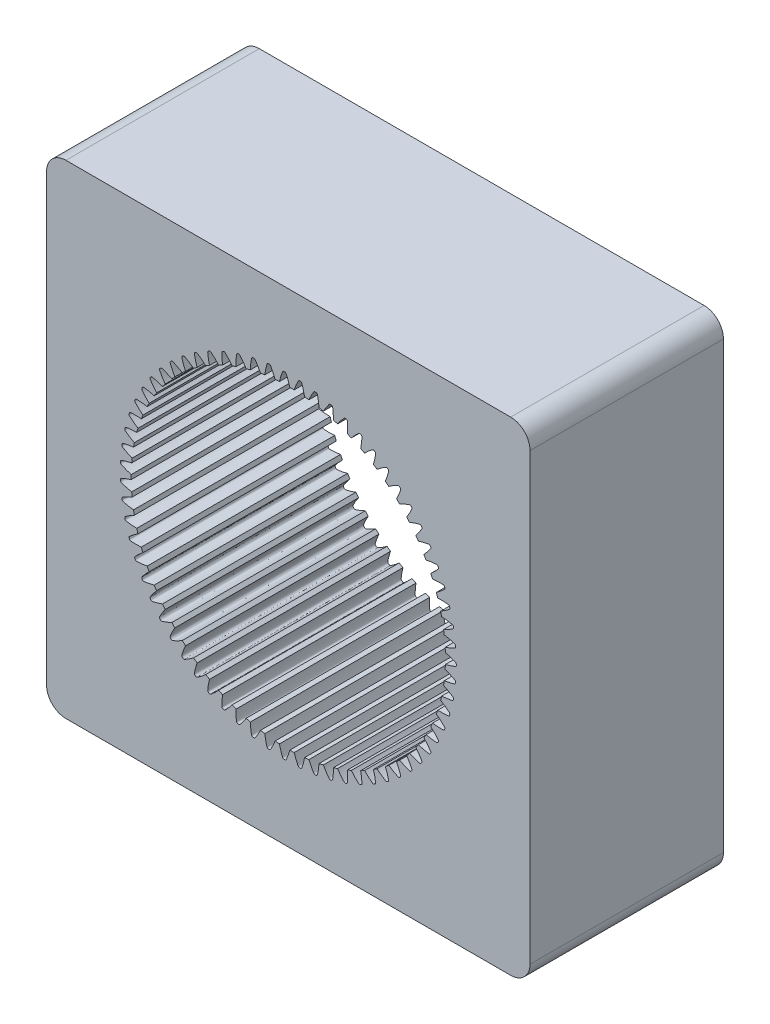
SolidWorks part; units mm, degrees
ref_plane "Front" through (0, 0, 0) normal (0, 0, 1) x (1, 0, 0)
ref_plane "Top" through (0, 0, 0) normal (0, 1, 0) x (1, 0, 0)
ref_plane "Right" through (0, 0, 0) normal (1, 0, 0) x (0, 0, -1)
ref_axis "Ось1" through (0, 0, 50) along (0, 0, -1)
sketch "SketchRevolveRing_Gear_Fixed01" plane through (0, 0, 0) normal (1, 0, 0) x (0, 0, -1)
  line L0 (0, 0) -> (1, 0) construction
  line L1 (-17.5, 16.25) -> (-17.5, 70)
  line L2 (-17.5, 70) -> (2.5, 70)
  line L3 (2.5, 70) -> (2.5, 16.25)
  line L4 (2.5, 16.25) -> (-17.5, 16.25)
  dimension "Side1" = 17.5
  dimension "OutsideRadius" = 70
  dimension "Side2" = 2.5
  dimension "MinorDiameter" = 16.25
revolve "Ring_Gear_Fixed01" add sketch "SketchRevolveRing_Gear_Fixed01" angle 360 about L0
sketch "SketchToothRing_Gear_Fixed01" plane through (0, 0, 0) normal (0, 0, 1) x (1, 0, 0)
  arc A0 (16.1448, -0.5551) -> (16.1448, 0.5551) centre (0, 0) ccw
  spline S0 degree 3 poles (16.1448, 0.5551) (16.203, 0.5437) (16.2937, 0.5237) (16.4187, 0.492) (16.5233, 0.4629) (16.6347, 0.4292) (16.7528, 0.3907) (16.8772, 0.3467) (17.0085, 0.2982) (17.1505, 0.2369) (17.2629, 0.2018) (17.323, 0.1588) (17.3383, 0.1435) (17.3514, 0.1262) (17.3618, 0.1072) (17.3719, 0.0804) (17.3754, 0.0515) (17.3749, 0.0224) (17.3751, 0) (17.3749, -0.0224) (17.3754, -0.0515) (17.3719, -0.0804) (17.3618, -0.1072) (17.3514, -0.1262) (17.3383, -0.1435) (17.323, -0.1588) (17.2629, -0.2018) (17.1505, -0.2369) (17.0085, -0.2982) (16.8772, -0.3467) (16.7528, -0.3907) (16.6347, -0.4292) (16.5233, -0.4629) (16.4187, -0.492) (16.2937, -0.5237) (16.203, -0.5437) (16.1448, -0.5551) knots 0 0 0 0 0.062627 0.098077 0.136285 0.17725 0.220974 0.267455 0.316694 0.36869 0.431293 0.438895 0.446497 0.454098 0.4617 0.469302 0.484196 0.492098 0.5 0.507902 0.515804 0.530698 0.5383 0.545902 0.553503 0.561105 0.568707 0.63131 0.683306 0.732545 0.779026 0.82275 0.863715 0.901923 0.937373 1 1 1 1
extrude "ToothExtrudeCutRing_Gear_Fixed01" cut sketch "SketchToothRing_Gear_Fixed01" against normal blind 2.5 and the other way blind 17.5
ref_axis "Ось2" through (80.9, 0, 0) along (-1, 0, 0)
ref_plane "Плоскость1" through (0, 0, 0) normal (0, 0, -1) x (1, 0, 0)
pattern_circular "PatternRing_Gear_Fixed01" count 67 every 5.373 about axis through (0, 0, 50) along (0, 0, -1) of "ToothExtrudeCutRing_Gear_Fixed01"
sketch "AuxiliarySketchRing_Gear_Fixed01" plane through (0, 0, 0) normal (0, 0, 1) x (1, 0, 0)
  circle A0 centre (0, 0) radius 16.75 construction
  circle A1 centre (0, 0) radius 15.7399 construction
  circle A2 centre (0, 0) radius 17.375 construction
  circle A3 centre (0, 0) radius 16.25 construction
  dimension "PitchDiameter" = 33.5
  dimension "BaseDiameter" = 31.4797
  dimension "MajorDiameter" = 34.75
  dimension "MinorDiameter" = 32.5
sketch "Эскиз4" plane through (0, 0, 17.5) normal (0, 0, 1) x (1, 0, 0)
  line L1 (-25, -25) -> (25, -25)
  line L2 (-25, -25) -> (-25, 25)
  line L3 (-25, 25) -> (25, 25)
  line L4 (25, -25) -> (25, 25)
  line L5 (-25, -25) -> (25, 25) construction
  line L6 (-25, 25) -> (25, -25) construction
  point P0 (0, 0)
  dimension "D1" = 50
  dimension "D2" = 50
extrude "Вырез-Вытянуть2" cut sketch "Эскиз4" against normal blind 20 flip side to cut
fillet "Скругление1" radius 2 4 edges at (-25, 25, 7.5) (-25, -25, 7.5) (25, -25, 7.5) (25, 25, 7.5)
